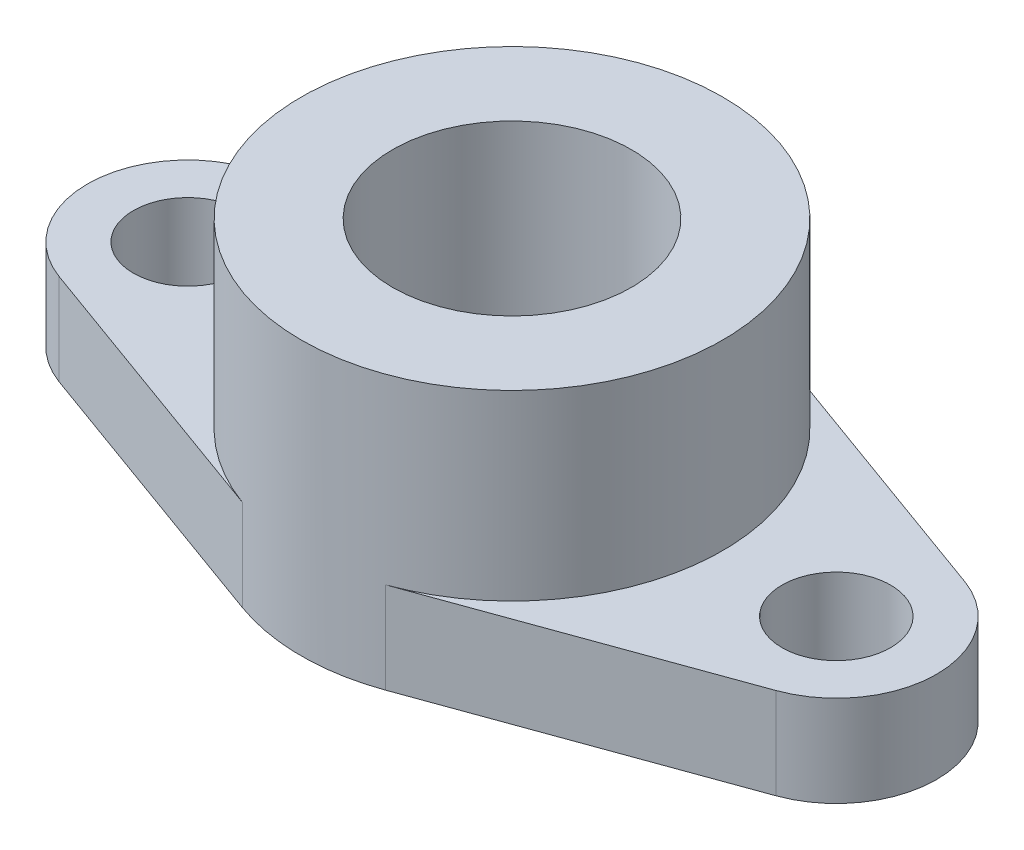
SolidWorks part; units mm, degrees
ref_plane "Front Plane" through (0, 0, 0) normal (0, 0, 1) x (1, 0, 0)
ref_plane "Top Plane" through (0, 0, 0) normal (0, 1, 0) x (1, 0, 0)
ref_plane "Right Plane" through (0, 0, 0) normal (1, 0, 0) x (0, 0, -1)
sketch "Sketch1" plane through (0, 0, 0) normal (0, 1, 0) x (1, 0, 0)
  line L0 (0, 0) -> (6.5484, 0) construction
  line L1 (0, 0) -> (17.78, 0) construction
  line L2 (19.651, 5.172) -> (3.9286, 10.8597)
  line L3 (3.9286, -10.8597) -> (19.651, -5.172)
  line L4 (0, 0) -> (-17.78, 0) construction
  line L5 (-19.651, 5.172) -> (-3.9286, 10.8597)
  line L6 (-19.651, -5.172) -> (-3.9286, -10.8597)
  circle A0 centre (0, 0) radius 4.826
  circle A1 centre (0, 0) radius 6.5484 construction
  arc A2 (3.9286, 10.8597) -> (3.9286, -10.8597) centre (0, 0) ccw construction
  circle A3 centre (17.78, 0) radius 2.9766
  arc A4 (19.651, -5.172) -> (19.651, 5.172) centre (17.78, 0) ccw
  circle A5 centre (0, 0) radius 11.5484 construction
  circle A6 centre (-17.78, 0) radius 2.9766
  arc A7 (-19.651, 5.172) -> (-19.651, -5.172) centre (-17.78, 0) ccw
  arc A10 (-3.9286, -10.8597) -> (3.9286, -10.8597) centre (0, 0) ccw
  arc A11 (3.9286, 10.8597) -> (-3.9286, 10.8597) centre (0, 0) ccw
  dimension "D1" = 9.652
  dimension "D2" = 13.0969
  dimension "D3" = 23.0969
  dimension "D5" = 5.9531
  dimension "D7" = 5.9531
  dimension "D6" = 5.5
  dimension "D4" = 17.78
  dimension "D8" = 17.78
extrude "Boss-Extrude1" add sketch "Sketch1" along normal blind 5
sketch "Sketch2" plane through (0, 5, 0) normal (0, 1, 0) x (1, 0, 0)
  circle A0 centre (0, 0) radius 11.5484
  arc A1 (-3.9286, -10.8597) -> (3.9286, -10.8597) centre (0, 0) ccw construction
  circle A2 centre (0, 0) radius 6.5484
  dimension "D1" = 13.0969
extrude "Boss-Extrude2" add sketch "Sketch2" along normal blind 10
equation "\"z\"= 8\t\t\t\t'number of blades"
equation "\"de\"= 0.43in\t\t\t'entrance eye diameter"
equation "\"de_length\"= 10mm\t\t'entrance eye consistent length"
equation "\"d_exit\"= 0.18in \t\t'throat aka d1"
equation "\"d2\"= 2.1in \t\t\t'outer diameter of the impeller"
equation "\"b2\"= .2in\t\t\t'tip height from disc surface at d2; slightly higher than d_exit"
equation "\"b1\"= \"b2\" + (\"d2\"/2 - \"de\"/2)*tan(\"theta\") \t\t\t'tip height from disc surface at inlet eye"
equation "\"theta\"= 12\t\t\t'angle of blades from inner to outer "
equation "\"ae\"= 3.14*(\"de\"^2)/4\t\t'entrance eye area'"
equation "\"ce\"= 3.14*\"de\"\t\t'entrance eye circumference"
equation "\"av_ratio\"= .325\t\t'ratio of av/ae at N_s of 470, range is .275 to .375, .325 ideal. High ratio means bigger area means smaller blades"
equation "\"av\"= \"ae\"*\"av_ratio\"\t\t'area between just two blades"
equation "\"s_open\"= \"av\"/\"b1\"\t\t'width of open area"
equation "\"s\"=\"ce\" - \"z\"*\"s_open\""
equation "\"min blade thickness\"= .15in"
equation "\"bearing OD\"= 30mm"
equation "\"bearing ID\"= 10mm"
equation "\"bearing depth\"= 9mm"
equation "\"bearing outer race thickness\"= 1mm"
equation "\"bearing inner race thickness\"= 1mm"
equation "\"bearing bore\"= \"bearing depth\" + 1mm"
equation "\"lower seal OD\"= .917in\t\t'this is https://www.mcmaster.com/#9281k121/=174001b"
equation "\"lower seal ID\"= .375in"
equation "\"lower seal depth\"= .625in + .218in"
equation "\"lower seal bore\"= \"lower seal depth\" + 1mm"
equation "\"upper seal OD\"= 1.125in\t'this is https://www.mcmaster.com/#5154t33/=173zuau, needs to be visually inspected before machining!"
equation "\"upper seal ID\"= 0.625in"
equation "\"upper seal depth\"= .25in\t'aka height; these values need to be confirmed by inspection!! We may want to compress the height."
equation "\"upper seal bore\"= \"upper seal depth\" + 1mm"
equation "\"big o-ring thickness\"= .139in"
equation "\"big o-ring OD\"= 2.734in"
equation "\"big o-ring ID\"= 3.012in"
equation "\"big o-ring groove depth\"= \"big o-ring thickness\"*4/5"
equation "\"impeller center height\"= \"impeller base thickness\" + \"b1\"\t'impeller height at de"
equation "\"impeller outer height\"= \"impeller base thickness\" + \"b2\"\t'impeller height at de"
equation "\"impeller upper clearance\"= .5mm"
equation "\"impeller horizontal clearance\"= (\"d2\"*1.15 - \"d2\")/2 \t\t'clearance based on D2-D3 ratio for circular volute, ranges 1.15 to 1.2"
equation "\"impeller bottom clearance\"= .5mm"
equation "\"impeller base thickness\"= 2mm"
equation "\"impeller dowel diameter\"= 2mm"
equation "\"impeller bolt head diameter\"= \"m4 head bore diameter\""
equation "\"impeller bolt head depth\"= 4mm"
equation "\"impeller bolt stop depth\"= 3mm"
equation "\"impeller bolt bore\"= \"m4 clearance\""
equation "\"impeller shaft bore depth\"= 12mm"
equation "\"impeller shaft bore\"= 8mm"
equation "\"impeller boss depth\"= \"impeller shaft bore depth\"+\"impeller bolt stop depth\"+\"impeller bolt head depth\"-\"impeller base thickness\""
equation "\"impeller boss diameter\"= \"upper seal ID\""
equation "\"impeller dowel length\"= 2mm*2 + \"impeller shaft bore\""
equation "\"coupler motor shaft hole ID\"= 8mm"
equation "\"coupler OD\"= 17mm"
equation "\"coupler length\"= 25mm"
equation "\"motor OD\"= 64mm"
equation "\"motor shaft diameter\"= 8mm"
equation "\"motor shaft pride\"= 32mm"
equation "\"motor to bearing plate distance\"= \"motor shaft pride\" + 2mm +\"coupler length\"/2"
equation "\"square plate bolt bore\"= \"m8 clearance\""
equation "\"square plate bolt head diameter\"= 13.5mm"
equation "\"square plate bolt head depth\"= 8mm"
equation "\"square plate bolt pattern diameter\"= 3.5in"
equation "\"motor mount center bore\"= \"coupler OD\"+ 4mm"
equation "\"motor mount post radius\"= ( 3 * \"square plate bolt bore\" ) / 2"
equation "\"motor mount m4 screw hole diameter\"= 4mm"
equation "\"motor mount m4 head diameter\"= 7.25mm"
equation "\"motor mount m4 head depth\"= 4mm"
equation "\"motor mount m4 pattern diamater\"= 30mm"
equation "\"motor mount plate thickness\"= 8mm + \"motor mount m4 head depth\""
equation "\"bearing plate stop ID\"= \"bearing OD\" - 4mm"
equation "\"bearing plate stop depth\"= 3mm"
equation "\"bearing plate thickness\"= \"bearing bore\" + \"bearing plate stop depth\" + \"shaft bearing stop length\""
equation "\"lower seal plate lip depth\"= 2mm"
equation "\"lower seal plate lip ID\"= \"lower seal OD\" - 3mm"
equation "\"lower seal plate thickness\"= \"lower seal plate lip depth\" + \"lower seal bore\""
equation "\"shaft coupler section diameter\"= 8mm"
equation "\"shaft coupler section length\"= \"motor to bearing plate distance\" - \"motor shaft pride\" - 2mm"
equation "\"shaft bearing section diameter\"= \"bearing ID\""
equation "\"shaft bearing section length\"= \"bearing plate stop depth\" + \"bearing depth\""
equation "\"shaft bearing stop diameter\"= \"bearing ID\" + 4mm"
equation "\"shaft bearing stop length\"= 3mm"
equation "\"shaft lower seal section diameter\"= \"lower seal ID\""
equation "\"shaft lower seal section length\"= \"lower seal plate thickness\" + 1mm"
equation "\"shaft impeller section diameter\"= \"impeller shaft bore\""
equation "\"shaft impeller section length\"= \"upper seal plate thickness\" + \"upper seal plate riser\" + \"impeller bottom clearance\" + \"impeller base thickness\" - \"impeller bolt head depth\" - \"impeller bolt stop depth\""
equation "\"upper seal plate thickness\"= \"upper seal plate pressure hole diameter\"+10mm"
equation "\"upper seal plate lip ID\"= \"upper seal OD\" - 3mm"
equation "\"upper seal plate riser\"= 6.59mm \t\t'this number needs to be read from the housing file"
equation "\"upper seal plate pressure hole diameter\"= .125in\t'this is 1/8 drill "
equation "\"upper seal plate pressure tap diameter\"= .328125in \t'this is 21/64 drill for a 1/8 ANPT tap"
equation "\"upper seal plate pressure tap grip\"= 5mm\t\t'this is the area around the tap so it doesn't crack"
equation "\"upper seal plate pressure tap depth\"= 12mm"
equation "\"impeller cavity center height\"= \"impeller bottom clearance\" + \"impeller upper clearance\" + \"impeller center height\""
equation "\"impeller cavity diameter\"= 2 * \"impeller horizontal clearance\" + \"d2\" \t\t\t\t\t\t\t\t\t'called D3 analytically"
equation "\"impeller cavity outer height\"= \"impeller bottom clearance\" + \"impeller upper clearance\" + \"impeller base thickness\" + \"b2\" \t\t'this is height at impeller diameter d2, not at d3"
equation "\"impeller housing thickness\"= \"impeller housing exit threaded diameter\" + 2*\"impeller housing outlet grip\""
equation "\"impeller housing diameter\"= \"square plate bolt pattern diameter\" + 2*\"motor mount post radius\""
equation "\"impeller housing bolt count\"= 6"
equation "\"impeller housing bolt diameter\"= \"m6 clearance\""
equation "\"impeller housing bolt pattern diameter\"= 3.5in"
equation "\"impeller housing threaded inlet diameter\"= 0.515625in \t'this is the 33/64 drill size for 9/16-18 fitting, expecting swagelok SS-8FK0-1-6STH fitting"
equation "\"impeller housing threaded inlet depth\"= 10mm"
equation "\"impeller housing exit threaded diameter\"= 0.515625in \t\t'this is the 33/64 drill size for 9/16-18 fitting, expecting swagelok SS-8FK0-1-6STH fitting"
equation "\"impeller housing exit threaded depth\"= 10mm"
equation "\"impeller housing diffuser conical angle\"=10"
equation "\"impeller housing diffuser tangent angle\"=5"
equation "\"impeller housing diffuser final diameter\"= .38in\t\t'aka d2'"
equation "\"impeller housing outlet grip\"= 5mm"
equation "\"end mill size\"= 0.375in\t'for 3/8 endmill"
equation "\"m4 clearance\"= 0.171875in \t'this is 11/64 bit for 4.36mm"
equation "\"m4 tap\"= 0.125in\t\t'this is 1/8 bit for 3.17mm"
equation "\"m4 head bore diameter\"= 7.5mm"
equation "\"m4 head bore depth\"= 5mm\t'actual is ~4mm"
equation "\"m6 clearance\"= 0.234375in\t'this is 15/64 bit = 5.95mm, could use 6mm bit, B bit for 6.04mm or 1/4 bit for 6.35mm"
equation "\"m6 tap\"= 5mm\t\t\t'5mm is appropriate, could use 13/64 or #5,6,7"
equation "\"m6 head bore diameter\"= 11mm\t\t"
equation "\"m6 head bore depth\"= 7mm\t'actual is 6mm"
equation "\"m8 clearance\"= 0.3125in\t'this is 5/16in for 7.93mm, could use 8mm, O,P, or 21/64"
equation "\"m8 tap\"= 0.265625in\t\t'this is 17/64 for 6.746875mm"
equation "\"m8 head bore diameter\"= 14mm"
equation "\"m8 head bore depth\"= 9mm\t'actual is 8mm"
equation "\"D1@Sketch1\"=\"impeller housing diffuser final diameter\""
equation "\"D2@Sketch1\"=\"impeller housing exit threaded diameter\""
equation "\"D3@Sketch1\"=\"impeller housing exit threaded diameter\"+\"impeller housing outlet grip\"*2 "
equation "\"D5@Sketch1\"=\"m6 clearance\""
equation "\"D7@Sketch1\"=\"m6 clearance\""
equation "\"D6@Sketch1\"=\"m6 head bore diameter\"/2"
equation "\"D1@Sketch2\"=\"impeller housing exit threaded diameter\""
equation "\"D1@Boss-Extrude2\"=10mm"
equation "\"diffuser cartridge OD\"=.75in"
equation "\"diffuser flange bolt pattern diameter\"= 1.4in"
equation "\"D4@Sketch1\"=\"diffuser flange bolt pattern diameter\"/2"
equation "\"D8@Sketch1\"=\"diffuser flange bolt pattern diameter\"/2"
